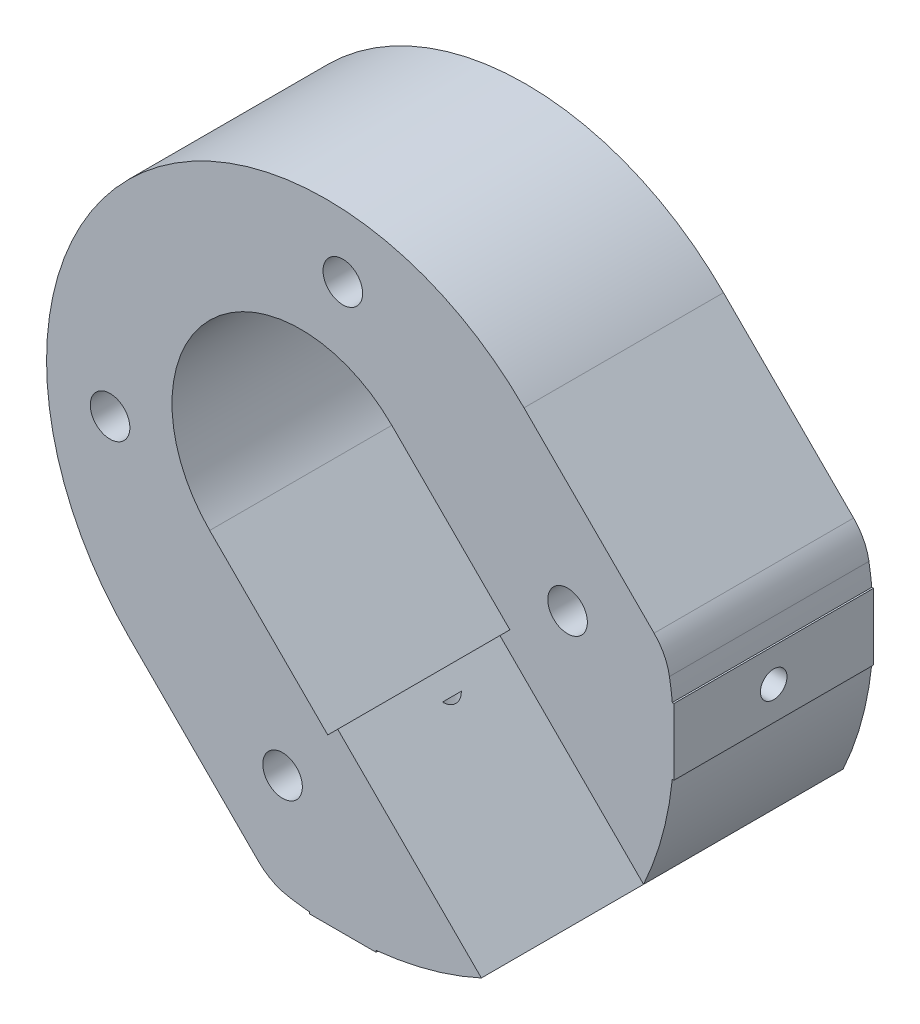
SolidWorks part; units mm, degrees
ref_plane "Front Plane" through (0, 0, 0) normal (0, 0, 1) x (1, 0, 0)
ref_plane "Top Plane" through (0, 0, 0) normal (0, 1, 0) x (1, 0, 0)
ref_plane "Right Plane" through (0, 0, 0) normal (1, 0, 0) x (0, 0, -1)
ref_axis "Z" through (0, 0, 33.5996) along (0, 0, -1)
ref_axis "X" through (56.0652, 0, 0) along (-1, 0, 0)
ref_axis "Y" through (0, -54.2845, 0) along (0, 1, 0)
sketch "Sketch1" plane through (0, 0, 0) normal (0, 0, 1) x (1, 0, 0)
  line L0 (5, -49.8046) -> (-5, -49.8046)
  line L1 (49.8046, 5) -> (49.8046, -5)
  line L2 (56.0652, 0) -> (-1.1166, 0) construction
  line L3 (0, -54.2845) -> (0, 1.1167) construction
  line L4 (61.712, 0) -> (49.8046, 0) construction
  line L5 (0, -49.8046) -> (0, -57.4075) construction
  line L6 (49.8046, -5) -> (49.553, -5)
  line L7 (5, -49.553) -> (5, -49.8046)
  line L10 (65.572, -65.572) -> (0, 0) construction
  line L20 (-5, -49.8046) -> (-5, -49.553)
  line L21 (49.553, 5) -> (49.8046, 5)
  line L22 (20.8398, -45.2349) -> (-0.7634, -23.6318)
  line L23 (45.2349, -20.8398) -> (23.6318, 0.7634)
  line L25 (-0.7634, -23.6318) -> (-2.2604, -25.1287)
  line L26 (-2.2604, -25.1287) -> (-20.0175, -7.3715)
  line L27 (23.6318, 0.7634) -> (25.1287, 2.2604)
  line L28 (25.1287, 2.2604) -> (7.3715, 20.0175)
  line L29 (-12.6664, -46.8192) -> (-32.232, -27.2537)
  line L30 (46.8192, 12.6664) -> (27.2537, 32.232)
  circle A0 centre (0, 0) radius 49.8046 construction
  circle A1 centre (0, 0) radius 3.535 construction
  arc A2 (49.553, -5) -> (5, -49.553) centre (0, 0) cw construction
  arc A6 (49.553, 5) -> (49.1286, 8.1778) centre (0, 0) ccw
  arc A7 (5, -49.553) -> (20.8398, -45.2349) centre (0, 0) ccw
  arc A8 (49.553, -5) -> (45.2349, -20.8398) centre (0, 0) cw
  arc A9 (7.3715, 20.0175) -> (-20.0175, -7.3715) centre (-6.323, 6.323) ccw
  arc A10 (-8.1778, -49.1286) -> (-12.6664, -46.8192) centre (-6.8202, -40.973) cw
  arc A12 (-8.1778, -49.1286) -> (-5, -49.553) centre (0, 0) ccw
  arc A13 (35.2172, -35.2172) -> (-8.1778, -49.1286) centre (0, 0) ccw construction
  arc A15 (49.1286, 8.1778) -> (46.8192, 12.6664) centre (40.973, 6.8202) ccw
  arc A17 (49.1286, 8.1778) -> (35.2172, -35.2172) centre (0, 0) ccw construction
  arc A18 (27.2537, 32.232) -> (-32.232, -27.2537) centre (-2.4891, 2.4891) ccw
  dimension "D1" = 99.6092
  dimension "D2" = 7.07
  dimension "D3" = 10
  dimension "D4" = 45
  dimension "D5" = 34.5
extrude "Boss-Extrude1" add sketch "Sketch1" against normal blind 15 and the other way blind 15
sketch "Sketch2" plane through (0, -49.8046, 0) normal (0, 1, 0) x (1, 0, 0)
  line L0 (-57.5886, 0) -> (57.5886, 0) construction
  line L1 (0, -20.5521) -> (0, 20.5521) construction
  circle A0 centre (0, 0) radius 2
  dimension "D1" = 4
extrude "Cut-Extrude1" cut sketch "Sketch2" along normal blind 24
sketch "Sketch3" plane through (49.8046, 0, 0) normal (1, 0, 0) x (0, 0, -1)
  circle A0 centre (0, 0) radius 2
  dimension "D1" = 4
extrude "Cut-Extrude2" cut sketch "Sketch3" against normal blind 24
sketch "Sketch5" plane through (0, 0, 0) normal (0, 0, 1) x (1, 0, 0)
  line L0 (0, 0) -> (0, -66.8046) construction
  dimension "D1" = 66.8046
ref_plane "Vert" through (0, 0, 0) normal (0.7071, 0.7071, 0) x (0, 0, -1)
sketch "Sketch6" plane through (0, 0, 0) normal (0, 0, 1) x (1, 0, 0)
  line L0 (0, 0) -> (-9.0587, -33.8074) construction
  line L1 (0, 0) -> (18.8244, -18.8244) construction
  line L2 (0, -54.2845) -> (0, 1.1167) construction
  line L3 (0, 0) -> (-35, 0) construction
  circle A0 centre (-9.0587, -33.8074) radius 2.9766
  circle A1 centre (-35, 0) radius 2.9766
  circle A2 centre (0, 35) radius 2.9766
  circle A3 centre (33.8074, 9.0587) radius 2.9766
  dimension "D4" = 5.9531
  dimension "D1" = 35
  dimension "D2" = 45
  dimension "D3" = 60
extrude "Cut-Extrude4" cut sketch "Sketch6" along normal through all
equation "\"EyeDiameter\" = 99.60916292"
equation "\"BasePlaneDistance\" = \"EyeDiameter\"/2+\"L2Thickness\"+\"EyeClearance\""
equation "\"EyeClearance\" = 2"
equation "\"EyeOD\"= \"EyeDiameter\""
equation "\"D2@Sketch1\"= 7.07"
equation "\"pinHoleDiameter\"=4"
equation "\"D1@Sketch2\"=\"pinHoleDiameter\""
equation "\"D1@Sketch3\"=\"pinHoleDiameter\""
equation "\"D1@Sketch5\"=\"BasePlaneDistance\""
equation "\"L2_ID\" = 20"
equation "\"vx\" = 0"
equation "\"vy\" = 0"
equation "\"vz\" = 200"
equation "\"parametric_end\" = 1"
equation "\"Rw_3_xx\" = -(\"vz\")/sqr((\"vx\")^2 + (\"vz\")^2)"
equation "\"Rw_3_xy\" = 0"
equation "\"Rw_3_xz\" = (\"vx\")/sqr((\"vx\")^2 + (\"vz\")^2)"
equation "\"Rw_3_zx\" = (\"vx\")/sqr((\"vx\")^2 + (\"vy\")^2 + (\"vz\")^2)"
equation "\"Rw_3_zy\" = (\"vy\")/sqr((\"vx\")^2 + (\"vy\")^2 + (\"vz\")^2)"
equation "\"Rw_3_zz\" = (\"vz\")/sqr((\"vx\")^2 + (\"vy\")^2 + (\"vz\")^2)"
equation "\"Rw_3_yx\" = (\"vx\")*(\"vy\")/sqr((\"vx\")^4 + (\"vx\")^2*(\"vy\")^2 + 2*(\"vx\")^2*(\"vz\")^2 + (\"vy\")^2*(\"vz\")^2 + (\"vz\")^4)"
equation "\"Rw_3_yy\" = -sqr((\"vx\")^2 + (\"vz\")^2)/sqr((\"vx\")^2 + (\"vy\")^2 + (\"vz\")^2)"
equation "\"Rw_3_yz\" = (\"vy\")*(\"vz\")/sqr((\"vx\")^4 + (\"vx\")^2*(\"vy\")^2 + 2*(\"vx\")^2*(\"vz\")^2 + (\"vy\")^2*(\"vz\")^2 + (\"vz\")^4)"
equation "\"O2Targx\" = -\"BasePlaneDistance\"*(\"vx\")*(\"vy\")/sqr((\"vx\")^4 + (\"vx\")^2*(\"vy\")^2 + 2*(\"vx\")^2*(\"vz\")^2 + (\"vy\")^2*(\"vz\")^2 + (\"vz\")^4)"
equation "\"O2Targy\" = \"BasePlaneDistance\"*sqr((\"vx\")^2 + (\"vz\")^2)/sqr((\"vx\")^2 + (\"vy\")^2 + (\"vz\")^2)"
equation "\"O2Targz\" = -\"BasePlaneDistance\"*(\"vy\")*(\"vz\")/sqr((\"vx\")^4 + (\"vx\")^2*(\"vy\")^2 + 2*(\"vx\")^2*(\"vz\")^2 + (\"vy\")^2*(\"vz\")^2 + (\"vz\")^4)"
equation "\"O2Targx_0\" = -(\"BasePlaneDistance\")*sqr((\"vx\")^2 + (\"vz\")^2)/sqr((\"vx\")^2 + (\"vy\")^2 + (\"vz\")^2)"
equation "\"O2Targy_0\" = -(\"BasePlaneDistance\")*(\"vy\")*(\"vz\")/sqr((\"vx\")^4 + (\"vx\")^2*(\"vy\")^2 + 2*(\"vx\")^2*(\"vz\")^2 + (\"vy\")^2*(\"vz\")^2 + (\"vz\")^4)"
equation "\"O2Targz_0\" = (\"BasePlaneDistance\")*(\"vx\")*(\"vy\")/sqr((\"vx\")^4 + (\"vx\")^2*(\"vy\")^2 + 2*(\"vx\")^2*(\"vz\")^2 + (\"vy\")^2*(\"vz\")^2 + (\"vz\")^4) + (\"BasePlaneDistance\")"
equation "\"theta2_s1\" = arcsin(((\"BasePlaneDistance\") - (\"O2Targz_0\"))/(\"BasePlaneDistance\")) + pi"
equation "\"theta2_s2\" = -arcsin(((\"BasePlaneDistance\") - (\"O2Targz_0\"))/(\"BasePlaneDistance\"))"
equation "\"theta1_s1\" = arcsin((\"O2Targy_0\")/((\"BasePlaneDistance\")*cos((\"Theta2\")))) + pi"
equation "\"theta1_s2\" = -arcsin((\"O2Targy_0\")/((\"BasePlaneDistance\")*cos((\"Theta2\"))))"
equation "\"theta1_s3\" = -arccos(-(\"O2Targx_0\")/((\"BasePlaneDistance\")*cos((\"Theta2\")))) + 2*pi"
equation "\"theta1_s4\" = arccos(-(\"O2Targx_0\")/((\"BasePlaneDistance\")*cos((\"Theta2\"))))"
equation "\"Theta1\" = \"theta1_s2\" 'so far, theta1_s1 and theta1_s4 have agreed, and they agree with the sw constraint solver"
equation "\"Theta2\" = \"theta2_s2\""
equation "\"o2_x\" = -(\"BasePlaneDistance\")*cos((\"Theta1\"))*cos((\"Theta2\"))"
equation "\"o2_y\" = -(\"BasePlaneDistance\")*sin((\"Theta1\"))*cos((\"Theta2\"))"
equation "\"o2_z\" = (\"BasePlaneDistance\")*(sin((\"Theta2\")) + 1)"
equation "\"o1_x\" = (\"BasePlaneDistance\")*sin((\"Theta1\"))"
equation "\"o1_y\" = -(\"BasePlaneDistance\")*cos((\"Theta1\"))"
equation "\"o1_z\" = (\"BasePlaneDistance\")"
equation "\"Actuator1_Theta\" = atn(\"vx\"/\"vz\") 'ik solution for the single link joint"
equation "\"Actuator2_Theta\" = \"Theta1\"  'ik solution for the double link joint"
equation "\"MotorBaseThickness\" = 3 "
equation "\"BaseThickness\" = 3 "
equation "\"EncoderToMagnetAirgap\" = 1 'Encoder to magnet airgap"
equation "\"EncoderHeight\" = 1.192  'Height of the encoder"
equation "\"MagnetThickness\" = 0.5  'Magnet thickness"
equation "\"pcb_thickness\" = 1.6  'Thickness of the PCB"
equation "\"pcb_outer_diameter\" = 32 'the OD of the pcb"
equation "\"shaft_diameter\" = 4"
equation "\"L2Thickness\" = 3.75 * \"shaft_diameter\""
equation "\"D1@Cut-Extrude2\"=\"shaft_diameter\"*6"
equation "\"D1@Cut-Extrude1\"=\"shaft_diameter\"*6"
equation "\"D1@Sketch1\"=\"EyeDiameter\""
